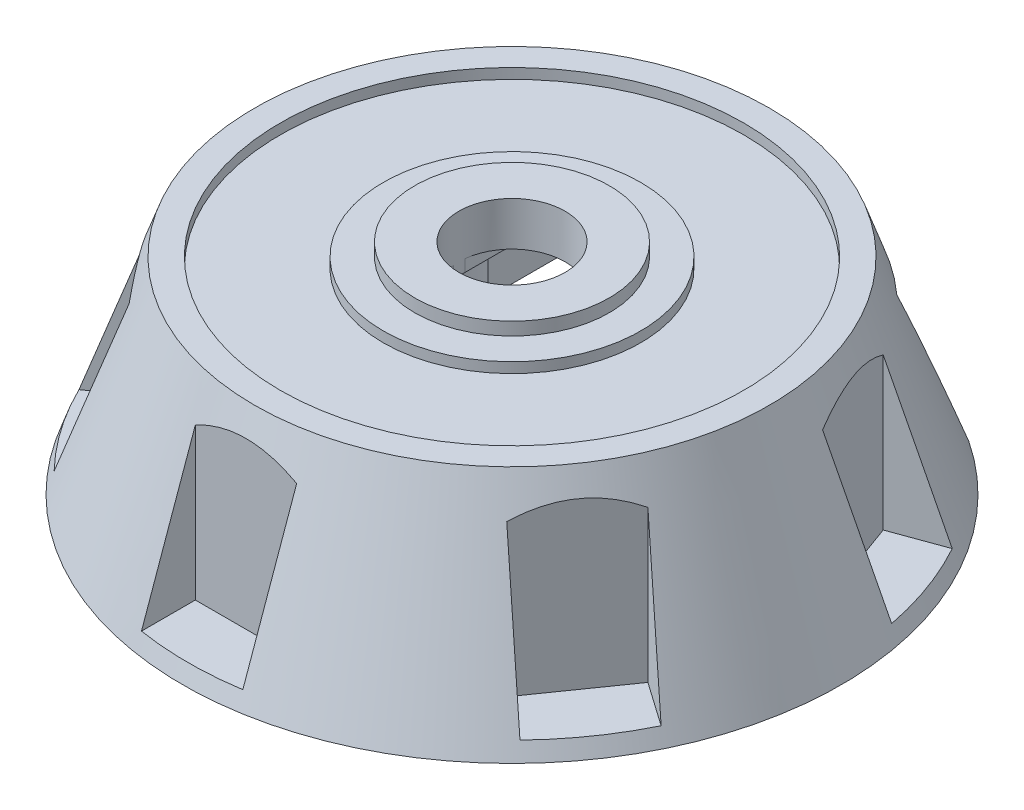
SolidWorks part; units mm, degrees
ref_plane "Front Plane" through (0, 0, 0) normal (0, 0, 1) x (1, 0, 0)
ref_plane "Top Plane" through (0, 0, 0) normal (0, 1, 0) x (1, 0, 0)
ref_plane "Right Plane" through (0, 0, 0) normal (1, 0, 0) x (0, 0, -1)
sketch "Sketch3" plane through (0, 0, 0) normal (0, 0, 1) x (1, 0, 0)
  line L0 (60.96, 0) -> (81.28, 0)
  line L1 (0, 0) -> (60.96, 0)
  line L2 (0, 0) -> (0, 50.8)
  line L3 (0, 50.8) -> (63.5, 50.8)
  line L5 (63.5, 50.8) -> (81.28, 0)
  point P5 (70.2105, 50.8)
  point P6 (0, 0)
  dimension "D1" = 50.8
  dimension "D2" = 63.5
  dimension "D3" = 53.8216
  dimension "D4" = 60.96
  dimension "D5" = 20.32
revolve "Revolve1" add sketch "Sketch3" angle 360 about L2
sketch "Sketch4" plane through (0, 0, 0) normal (0, -1, 0) x (-1, 0, 0)
  line L8 (-45, 39.0789) -> (-45, 81.5407)
  line L9 (-45, 81.5407) -> (45, 81.5407)
  line L10 (45, 39.0789) -> (45, 81.5407)
  arc A0 (-45, 39.0789) -> (45, 39.0789) centre (0, 0) ccw
  circle A1 centre (0, 0) radius 81.28 construction
  dimension "D1" = 59.6
  dimension "D2" = 45
  dimension "D3" = 81.5407
extrude "Cut-Extrude1" cut sketch "Sketch4" against normal blind 40.2 contours L10 L9 L8 A0
sketch "Sketch5" plane through (0, 50.8, 0) normal (0, 1, 0) x (1, 0, 0)
  circle A0 centre (0, 0) radius 13.1
  circle A1 centre (0, 0) radius 24
  circle A2 centre (0, 0) radius 63.5 construction
  dimension "D1" = 26.2
  dimension "D2" = 48
extrude "Cut-Extrude2" cut sketch "Sketch5" along direction (0, -1, 0) on the side against the normal up to next (10.6 mm away) contours A0
extrude "Boss-Extrude1" add sketch "Sketch5<3>" along normal blind 3.175
sketch "Sketch5<3>" plane through (0, 50.8, 0) normal (0, 1, 0) x (1, 0, 0) same geometry as "Sketch5"
sketch "Sketch6" plane through (0, 50.8, 0) normal (0, 1, 0) x (1, 0, 0)
  line L0 (0, 0) -> (0, -80) construction
  line L2 (12.5, -65.6081) -> (-12.5, -65.6081)
  line L3 (12.5, -65.6081) -> (12.5, -94.3919)
  line L4 (12.5, -94.3919) -> (-12.5, -94.3919)
  line L5 (-12.5, -65.6081) -> (-12.5, -94.3919)
  circle A0 centre (0, 0) radius 63.5 construction
  dimension "D1" = 12.5
  dimension "D2" = 12.5
  dimension "D3" = 65.6081
  dimension "D4" = 94.3919
extrude "Cut-Extrude3" cut sketch "Sketch6" against normal offset from surface (46.8 mm away) 4 contours L4 L5 L2 L3 up to face at (0, 0, 8.5287)
pattern_circular "CirPattern1" count 3 every 55 about axis through (0, 0, 0) along (0, 1, 0) of "Cut-Extrude3" reverse direction yes
pattern_circular "CirPattern2" count 3 every 55 about axis through (0, 0, 0) along (0, 1, 0) of "Cut-Extrude3"
sketch "Sketch7" plane through (0, 40.2, 0) normal (0, -1, 0) x (1, 0, 0)
  line L4 (0, -33) -> (0, 23.8422) construction
  line L5 (12.2, -4.5789) -> (-12.2, -4.5789) construction
  line L6 (45, -39.0789) -> (45, -49.9218) construction
  line L7 (13.0268, 18.6285) -> (-13.0268, 18.6285)
  line L8 (13.0268, 18.6285) -> (13.0268, -27.7863)
  line L9 (13.0268, -27.7863) -> (-13.0268, -27.7863)
  line L10 (-13.0268, 18.6285) -> (-13.0268, -27.7863)
  line L11 (13.0268, 18.6285) -> (-13.0268, -27.7863) construction
  line L12 (13.0268, -27.7863) -> (-13.0268, 18.6285) construction
  point P4 (0, -4.5789)
  dimension "D1" = 31.9732
  dimension "D2" = 45
  dimension "D3" = 11.2926
  dimension "D4" = 34.5
extrude "Cut-Extrude4" cut sketch "Sketch7" against normal blind 2.95
sketch "Sketch8" plane through (0, 40.2, 0) normal (0, -1, 0) x (1, 0, 0)
  circle A0 centre (15, -12.5) radius 1.4
  circle A1 centre (15, -29.5) radius 1.4
  circle A2 centre (8.5, -35.8) radius 1.4
  circle A3 centre (-8.5, -35.8) radius 1.4
  circle A4 centre (-15, -29.5) radius 1.4
  circle A5 centre (-15, -12.5) radius 1.4
  circle A6 centre (-15, 4.5) radius 1.4
  circle A7 centre (15, 4.5) radius 1.4
hole_wizard "M2.5 Clearance Hole1" positions "Sketch9" profile "Sketch10" hole size "M2.5" standard "ANSI Metric"
sketch "Sketch9" plane through (0, 40.2, 0) normal (0, -1, 0) x (-1, 0, 0)
  point P0 (-15, -4.5)
  point P3 (15, -4.5)
  point P6 (15, 12.5)
  point P9 (-15, 12.5)
  point P12 (15, 29.5)
  point P15 (-15, 29.5)
  point P18 (-8.5, 35.8)
  point P21 (8.5, 35.8)
sketch "Sketch10" plane through (15, 40.2, 4.5) normal (1, 0, 0) x (0, 0, -1)
  line L0 (0, 0) -> (0, 6.8712)
  line L1 (0, 6.8712) -> (1.45, 6)
  line L2 (1.45, 6) -> (1.45, 0)
  line L5 (1.45, 0) -> (0, 0)
  line L10 (0, 6.8712) -> (-1.45, 6) construction
  line L11 (0, -6.35) -> (0, 107.95) construction
  dimension "Hole Dia." = 2.9
  dimension "Hole Depth" = 6
  dimension "Drill Angle" = 118
sketch "Sketch11" plane through (0, 50.8, 0) normal (0, 1, 0) x (1, 0, 0)
  circle A0 centre (0, 0) radius 31.75
  circle A1 centre (0, 0) radius 57.15
  dimension "D1" = 25.4
  dimension "D2" = 63.5
extrude "Cut-Extrude5" cut sketch "Sketch11" against normal blind 2.54
